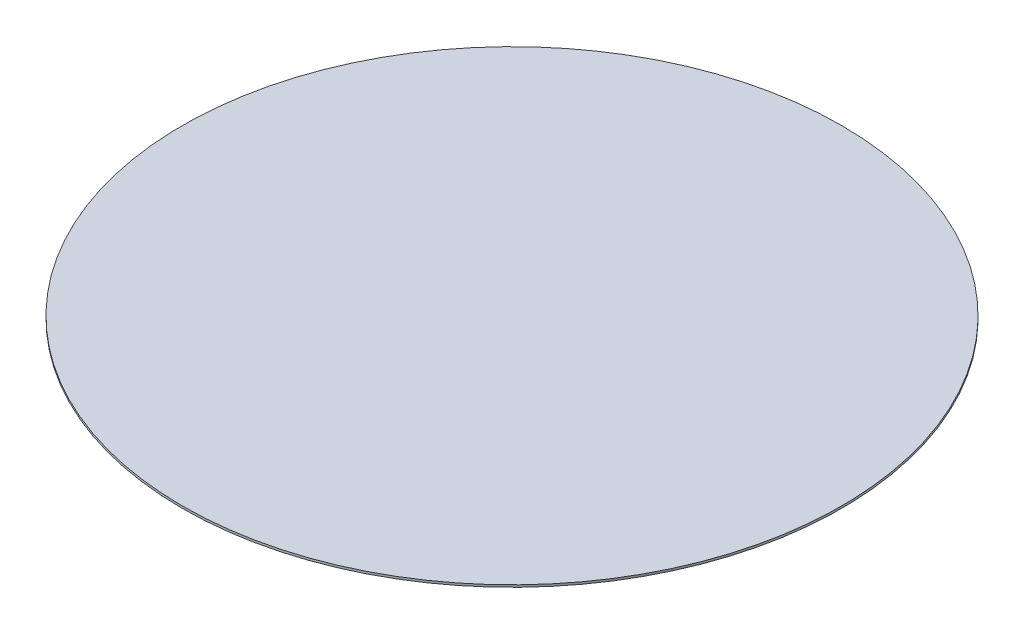
SolidWorks part; units mm, degrees
ref_plane "Front Plane" through (0, 0, 0) normal (0, 0, 1) x (1, 0, 0)
ref_plane "Top Plane" through (0, 0, 0) normal (0, 1, 0) x (1, 0, 0)
ref_plane "Right Plane" through (0, 0, 0) normal (1, 0, 0) x (0, 0, -1)
sketch "Sketch1" plane through (0, 0, 0) normal (0, 1, 0) x (1, 0, 0)
  circle A0 centre (0, 0) radius 38.1
  dimension "D1" = 76.2
extrude "Boss-Extrude1" add sketch "Sketch1" along normal blind 0.254
ref_axis "Axis1" through (0, 0.2667, 0) along (0, -1, 0)
